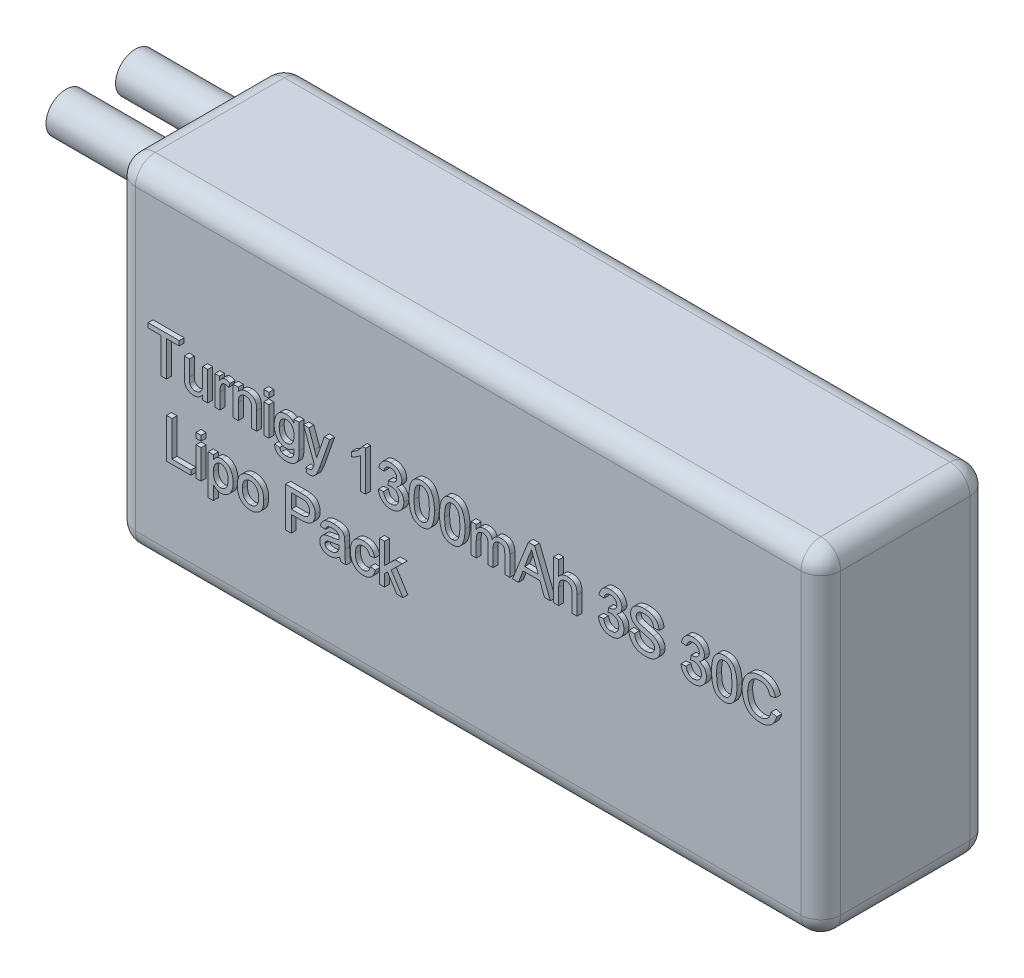
SolidWorks part; units mm, degrees
ref_plane "Спереди" through (0, 0, 0) normal (0, 0, 1) x (1, 0, 0)
ref_plane "Сверху" through (0, 0, 0) normal (0, 1, 0) x (1, 0, 0)
ref_plane "Справа" through (0, 0, 0) normal (1, 0, 0) x (0, 0, -1)
sketch "Эскиз1" plane through (0, 0, 0) normal (0, 0, 1) x (1, 0, 0)
  line L1 (-35.5, 17) -> (35.5, 17)
  line L2 (-35.5, 17) -> (-35.5, -17)
  line L3 (-35.5, -17) -> (35.5, -17)
  line L4 (35.5, 17) -> (35.5, -17)
  line L5 (-35.5, 17) -> (35.5, -17) construction
  line L6 (-35.5, -17) -> (35.5, 17) construction
  point P0 (0, 0)
  dimension "D1" = 71
  dimension "D2" = 34
extrude "Бобышка-Вытянуть1" add sketch "Эскиз1" along normal mid plane 17
sketch "Эскиз2" plane through (-35.5, 0, 0) normal (-1, 0, 0) x (0, 0, 1)
  line L0 (-3.5, 13) -> (3.5, 13) construction
  line L1 (0, 13) -> (0, 17) construction
  line L2 (8.5, 17) -> (-8.5, 17) construction
  circle A0 centre (-3.5, 13) radius 2
  circle A1 centre (3.5, 13) radius 2
  dimension "D1" = 4
  dimension "D2" = 7
  dimension "D3" = 4
extrude "Бобышка-Вытянуть2" add sketch "Эскиз2" along normal blind 10
sketch "Эскиз3" plane through (0, 0, 8.5) normal (0, 0, 1) x (1, 0, 0)
  text T0 "Turnigy 1300mAh 3S 30C\r\n Lipo Pack"
extrude "Бобышка-Вытянуть3" add sketch "Эскиз3" along normal blind 0.5
fillet "Redondeo2" radius 2 12 edges at (-35.5, 17, 0) (-35.5, -17, 0) (35.5, 17, 0) (35.5, -17, 0) (35.5, 0, 8.5) (0, -17, 8.5) (0, 17, 8.5) (-35.5, 0, 8.5) (-35.5, 0, -8.5) (0, -17, -8.5) (35.5, 0, -8.5) (0, 17, -8.5)
